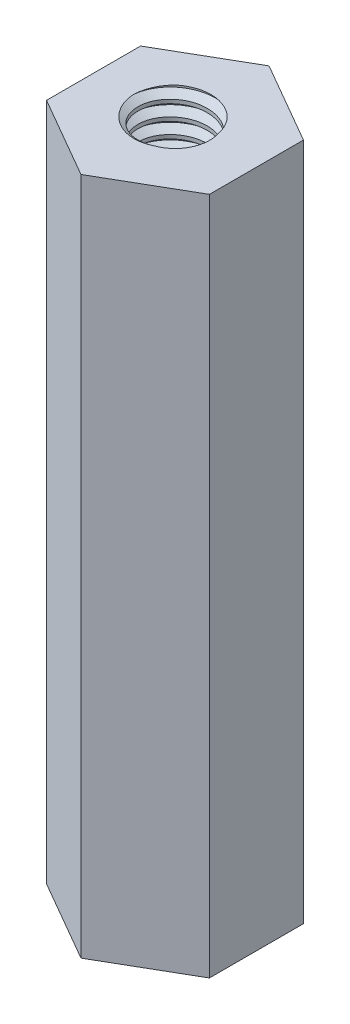
SolidWorks part; units mm, degrees
ref_plane "Front Plane" through (0, 0, 0) normal (0, 0, 1) x (1, 0, 0)
ref_plane "Top Plane" through (0, 0, 0) normal (0, 1, 0) x (1, 0, 0)
ref_plane "Right Plane" through (0, 0, 0) normal (1, 0, 0) x (0, 0, -1)
sketch "Sketch1" plane through (0, 0, 0) normal (0, 1, 0) x (1, 0, 0)
  line L1 (2.4, 1.3856) -> (0, 2.7713)
  line L2 (0, 2.7713) -> (-2.4, 1.3856)
  line L3 (-2.4, 1.3856) -> (-2.4, -1.3856)
  line L4 (-2.4, -1.3856) -> (0, -2.7713)
  line L5 (0, -2.7713) -> (2.4, -1.3856)
  line L6 (2.4, -1.3856) -> (2.4, 1.3856)
  circle A0 centre (0, 0) radius 2.4 construction
  circle A1 centre (0, 0) radius 1.025
  dimension "D1" = 4.8
  dimension "D2" = 2.05
extrude "Boss-Extrude1" add sketch "Sketch1" along normal mid plane 20
thread "Thread1" pitch 0.45 method cut profile "Thread Profile1" start angle 0, offset 2, length 24, pitch 0.45, diameter 2.05
ref_plane "Plane1" through (-1.025, 12, 0) normal (0, 0, 1) x (-1, 0, 0)
sketch "Thread Profile1" plane through (-1.025, 12, 0) normal (0, 0, 1) x (-1, 0, 0)
  line L0 (0, 0) -> (0, 0.45) construction
  line L1 (0, 0) -> (0.2436, 0.1406)
  line L2 (0.2436, 0.1406) -> (0.2436, 0.1969)
  line L3 (0.2436, 0.1969) -> (0, 0.3375)
  line L4 (0.2436, 0.1687) -> (0, 0.1687) construction
  line L11 (0, 0) -> (0, 0.3375)
  point P2 (0, 0)
  dimension "Pitch" = 0.45
  dimension "Profile_Angle" = 60
  dimension "Profile_Land" = 0.0562
  dimension "Profile_Height" = 0.2436
sketch "Sketch2" plane through (0, 0, 0) normal (0, 1, 0) x (1, 0, 0)
  line L6 (2.4, -1.3856) -> (2.4, 1.3856)
  line L7 (2.4, 1.3856) -> (0, 2.7713)
  line L8 (0, 2.7713) -> (-2.4, 1.3856)
  line L9 (-2.4, 1.3856) -> (-2.4, -1.3856)
  line L10 (-2.4, -1.3856) -> (0, -2.7713)
  line L11 (0, -2.7713) -> (2.4, -1.3856)
  line L12 (2.4, -1.3856) -> (2.4, 1.3856)
  line L13 (2.4, 1.3856) -> (0, 2.7713)
  line L14 (0, 2.7713) -> (-2.4, 1.3856)
  line L15 (-2.4, 1.3856) -> (-2.4, -1.3856)
  line L16 (-2.4, -1.3856) -> (0, -2.7713)
  line L17 (0, -2.7713) -> (2.4, -1.3856)
  dimension "D1" = 0
extrude "Boss-Extrude2" add sketch "Sketch2" along normal mid plane 10
